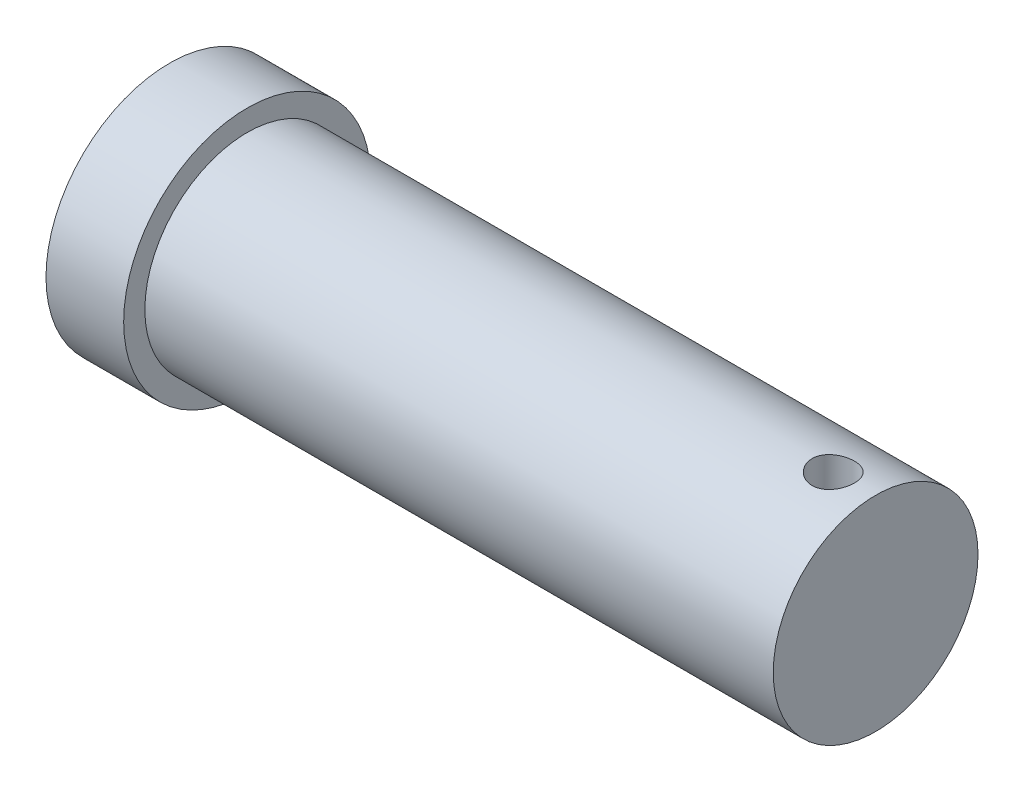
SolidWorks part; units mm, degrees
ref_plane "Front Plane" through (0, 0, 0) normal (0, 0, 1) x (1, 0, 0)
ref_plane "Top Plane" through (0, 0, 0) normal (0, 1, 0) x (1, 0, 0)
ref_plane "Right Plane" through (0, 0, 0) normal (1, 0, 0) x (0, 0, -1)
sketch "Sketch1" plane through (0, 0, 0) normal (1, 0, 0) x (0, 0, -1)
  circle A0 centre (0, 0) radius 2.9
  dimension "D1" = 5.8
extrude "Boss-Extrude1" add sketch "Sketch1" along normal blind 20
sketch "Sketch2" plane through (0, 0, 0) normal (0, 1, 0) x (1, 0, 0)
  line L0 (-55, 0) -> (55, 0) construction
  line L1 (0, 0) -> (1, 0) construction
  line L2 (18.8, 0) -> (20, 0) construction
  line L3 (20, -2.9) -> (20, 2.9) construction
  line L4 (18.8, 0) -> (14, 0) construction
  circle A1 centre (18.8, 0) radius 0.6
  dimension "D1" = 1.2
extrude "Cut-Extrude1" cut sketch "Sketch2" against normal blind 10 and the other way blind 10
sketch "Sketch3" plane through (0, 0, 0) normal (-1, 0, 0) x (0, 0, 1)
  circle A0 centre (0, 0) radius 3.5
extrude "Boss-Extrude2" add sketch "Sketch3" against normal blind 2.2
scale "Scale1" scale about origin uniform scaling yes scale factor 1.5
